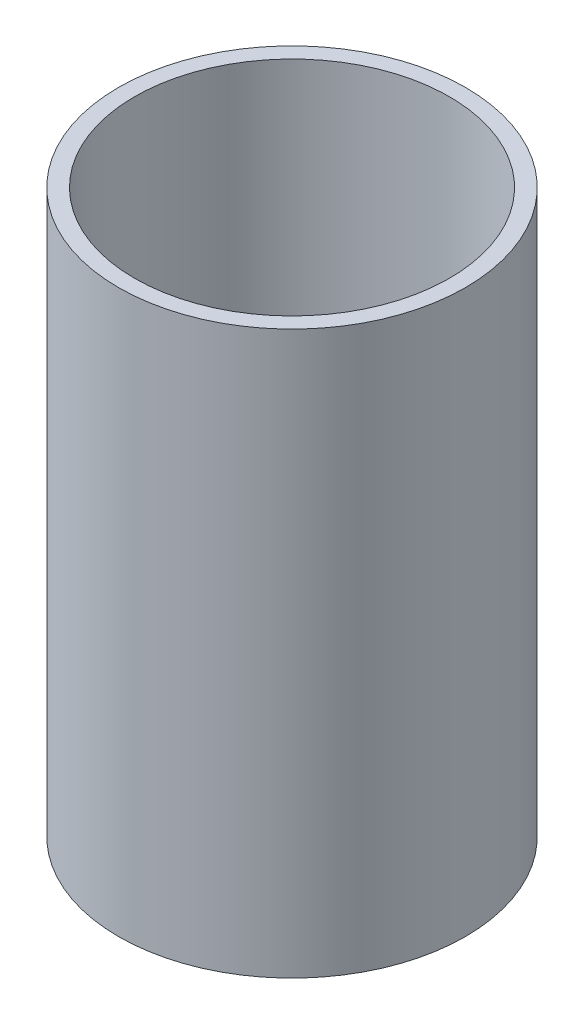
SolidWorks part; units mm, degrees
ref_plane "Front Plane" through (0, 0, 0) normal (0, 0, 1) x (1, 0, 0)
ref_plane "Top Plane" through (0, 0, 0) normal (0, 1, 0) x (1, 0, 0)
ref_plane "Right Plane" through (0, 0, 0) normal (1, 0, 0) x (0, 0, -1)
sketch "Sketch1" plane through (0, 0, 0) normal (0, 1, 0) x (1, 0, 0)
  line L0 (-5.25, 0.75) -> (-5.25, 0)
  line L1 (7.25, 0) -> (2.35, 0)
  line L2 (-2.35, 0) -> (-2.35, -1)
  line L3 (-2.35, -1) -> (2.35, -1)
  line L4 (-2.35, 0.75) -> (-2.35, 0)
  line L5 (-2.35, 0.75) -> (-2.35, 3)
  line L6 (2.35, 0.75) -> (2.35, 3)
  line L7 (5.25, 0.75) -> (5.25, 0)
  line L8 (-5.25, 3) -> (-5.25, 3.75)
  line L9 (-6.5, 3) -> (6.5, 3)
  line L10 (-2.35, 0.75) -> (-6.5, 0.75)
  line L11 (-7.25, 0) -> (-2.35, 0)
  line L12 (2.35, 0.75) -> (2.35, 0)
  line L13 (2.35, -1) -> (2.35, 0)
  line L14 (5.25, 3) -> (5.25, 3.75)
  line L15 (2.35, 0.75) -> (6.5, 0.75)
  line L17 (-6.5, 3) -> (-6.5, 0.75)
  line L18 (-7.25, 3.75) -> (7.25, 3.75)
  line L19 (6.5, 3) -> (6.5, 0.75)
  line L20 (-7.25, 3.75) -> (-7.25, 0)
  line L22 (7.25, 3.75) -> (7.25, 0)
  circle A15 centre (0, 0) radius 10.8
  circle A16 centre (0, 0) radius 9.8
  dimension "D1" = 0.75
  dimension "D2" = 0.75
  dimension "D3" = 0.75
  dimension "D4" = 0.75
  dimension "D5" = 2
  dimension "D6" = 2
  dimension "D7" = 4
  dimension "D8" = 4.15
  dimension "D9" = 4.15
extrude "Boss-Extrude7" add sketch "Sketch1" along normal blind 35 contours A15 A16 region at (-10.4945, 0, 0)
extrude "Boss-Extrude8" add sketch "Sketch1<10>" along normal blind 1 contours A16 L18 L22 L15 L19 L9 L17 L10 L11 L20 region at (-9.5228, 0, 0)
sketch "Sketch1<10>" plane through (0, 0, 0) normal (0, 1, 0) x (1, 0, 0) same geometry as "Sketch1"
extrude "Boss-Extrude9" add sketch "Sketch1<12>" along normal blind 5 contours L22 L18 L20 L11 L17 L9 L19 | L18 L8 L9 L14 | L22 L18 L14 L9 L19 L15 L7 L1 region at (-5.2925, 0, -0.375) region at (0, 0, -3.375) region at (5.2925, 0, -3.375)
sketch "Sketch1<12>" plane through (0, 0, 0) normal (0, 1, 0) x (1, 0, 0) same geometry as "Sketch1"
extrude "Boss-Extrude10" add sketch "Sketch1<13>" along normal blind 2 contours L11 L10 | L15 region at (-3.8, 0, -0.375) region at (3.8, 0, -0.375)
sketch "Sketch1<13>" plane through (0, 0, 0) normal (0, 1, 0) x (1, 0, 0) same geometry as "Sketch1"
extrude "Boss-Extrude11" add sketch "Sketch1<14>" along normal blind 0.5 contours L9 L17 L10 L5 | L19 L9 L6 L15 region at (-4.425, 0, -1.875) region at (4.425, 0, -1.875)
sketch "Sketch1<14>" plane through (0, 0, 0) normal (0, 1, 0) x (1, 0, 0) same geometry as "Sketch1"
extrude "Boss-Extrude12" add sketch "Sketch1<15>" along normal blind 20 contours L18 L20 L11 L0 L10 L17 L9 L8 | L22 L18 L14 L9 L19 L15 L7 L1 region at (-5.2925, 0, -0.375) region at (5.2925, 0, -3.375)
sketch "Sketch1<15>" plane through (0, 0, 0) normal (0, 1, 0) x (1, 0, 0) same geometry as "Sketch1"
